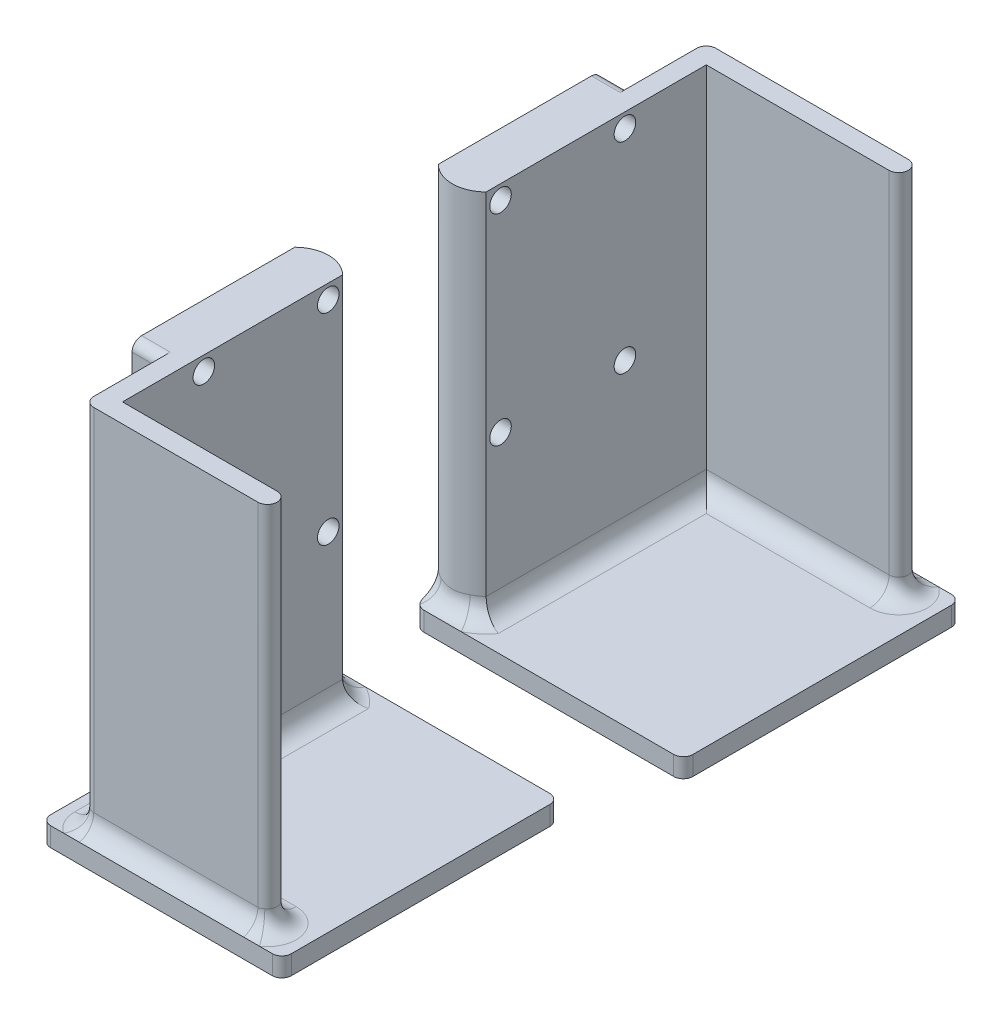
SolidWorks part; units mm, degrees
ref_plane "Front Plane" through (0, 0, 0) normal (0, 0, 1) x (1, 0, 0)
ref_plane "Top Plane" through (0, 0, 0) normal (0, 1, 0) x (1, 0, 0)
ref_plane "Right Plane" through (0, 0, 0) normal (1, 0, 0) x (0, 0, -1)
sketch "Sketch5" plane through (0, 0, 0) normal (0, 1, 0) x (1, 0, 0)
  line L0 (-1000, 0) -> (49000, 0) construction
sketch "Sketch1" plane through (0, 0, 0) normal (0, 1, 0) x (1, 0, 0)
  line L0 (-201000, 0) -> (249000, 0) construction
  line L1 (-28.1, 34) -> (0, 34)
  line L2 (-28.1, 34) -> (-28.1, 5)
  line L3 (-28.1, 5) -> (0, 5)
  line L4 (0, 34) -> (0, 5)
  line L5 (-28.1, 34) -> (0, 5) construction
  line L6 (-28.1, 5) -> (0, 34) construction
  line L7 (-55, 0) -> (55, 0) construction
  line L8 (-28.1, -5) -> (-2.95, -34) construction
  line L9 (-28.1, -34) -> (-2.95, -5) construction
  line L10 (-2.95, -34) -> (-2.95, -5)
  line L11 (-28.1, -5) -> (-2.95, -5)
  line L12 (-28.1, -34) -> (-28.1, -5)
  line L13 (-28.1, -34) -> (-2.95, -34)
  point P0 (-14.05, 19.5)
  point P14 (-13, -19.5)
  dimension "D1" = 29
  dimension "D2" = 28.1
  dimension "D3" = 5
  dimension "D4" = 0
  dimension "D5" = 25.15
extrude "Boss-Extrude1" add sketch "Sketch1" along normal blind 2
sketch "Sketch2" plane through (0, 2, 0) normal (0, 1, 0) x (1, 0, 0)
  line L0 (-28.1, 19.5) -> (0, 19.5) construction
  line L1 (-24.1, 31.5) -> (-24.1, 7.5) construction
  line L2 (-23.1, 31.5) -> (-23.1, 7.5)
  line L3 (-25.1, 31.5) -> (-25.1, 7.5)
  line L4 (0, 5) -> (0, 34)
  line L5 (0, 34) -> (-28.1, 34)
  line L6 (-28.1, 34) -> (-28.1, 5)
  line L7 (-28.1, 5) -> (0, 5)
  line L8 (0, 5) -> (0, 34)
  line L9 (0, 34) -> (-28.1, 34)
  line L10 (-28.1, 34) -> (-28.1, 5)
  line L11 (-28.1, 5) -> (0, 5)
  line L12 (-25.1, 7.5) -> (-23.1, 7.5) construction
  line L13 (-1000, 0) -> (49000, 0) construction
  line L16 (-24.1, 31.5) -> (-4, 31.5) construction
  line L17 (-24.1, 32.5) -> (-4, 32.5)
  line L18 (-24.1, 30.5) -> (-4, 30.5)
  line L19 (-24.1, -31.5) -> (-6.95, -31.5) construction
  line L23 (-25.1, 7.5) -> (-28.1, 7.5)
  line L24 (-24.1, -32.5) -> (-6.95, -32.5)
  line L25 (-24.1, -30.5) -> (-6.95, -30.5)
  line L26 (-23.1, -31.5) -> (-23.1, -7.5)
  line L27 (-25.1, -7.5) -> (-28.1, -7.5)
  line L28 (-25.1, -31.5) -> (-25.1, -7.5)
  line L29 (-2.95, -34) -> (-2.95, -5) construction
  arc A0 (-23.1, 31.5) -> (-25.1, 31.5) centre (-24.1, 31.5) ccw
  arc A4 (-24.1, 32.5) -> (-24.1, 30.5) centre (-24.1, 31.5) ccw
  arc A5 (-4, 30.5) -> (-4, 32.5) centre (-4, 31.5) ccw
  arc A8 (-23.1, 7.5) -> (-28.1, 7.5) centre (-25.6, 10) cw
  arc A9 (-24.1, -32.5) -> (-24.1, -30.5) centre (-24.1, -31.5) cw
  arc A10 (-6.95, -30.5) -> (-6.95, -32.5) centre (-6.95, -31.5) cw
  arc A11 (-23.1, -31.5) -> (-25.1, -31.5) centre (-24.1, -31.5) cw
  arc A12 (-23.1, -7.5) -> (-28.1, -7.5) centre (-25.6, -10) ccw
  point P8 (-24.15, 19.5)
  point P16 (-24.1, 7.5)
  point P18 (-15.525, -31.5)
  point P24 (-14.05, 31.5)
  dimension "D9" = 3.5355
  dimension "D2" = 24
  dimension "D3" = 2
  dimension "D4" = 3
  dimension "D5" = 2
  dimension "D6" = 4
  dimension "D7" = 4
  dimension "D8" = 2
  dimension "D10" = 2.5
  dimension "D1" = 0
extrude "Boss-Extrude2" add sketch "Sketch2" along normal blind 38.6 contours L3 L23 A8 L2 A0 | L18 A5 L17 A4 | A12 L27 L28 A11 L26 | L24 A10 L25 A9
sketch "Sketch3" plane through (-25.1, 0, 0) normal (-1, 0, 0) x (0, 0, 1)
  line L0 (-24.5, 39.6) -> (-24.5, 2)
  line L1 (-16, -972.3653) -> (-16, 49027.6347) construction
  line L2 (0, -1.1) -> (0, 1.1) construction
  line L3 (24.5, 39.6) -> (24.5, 2)
  line L4 (-31.5, 2) -> (-7.5, 2)
  line L5 (-7.5, 2) -> (-7.5, 40.6)
  line L6 (-7.5, 40.6) -> (-31.5, 40.6)
  line L7 (-31.5, 40.6) -> (-31.5, 2)
  line L8 (-31.5, 2) -> (-7.5, 2)
  line L10 (-7.5, 40.6) -> (-31.5, 40.6)
  line L11 (-31.5, 40.6) -> (-31.5, 2)
  line L12 (7.5, 40.6) -> (23.5, 40.6)
  line L13 (24.5, 2) -> (7.5, 2)
  line L14 (7.5, 2) -> (7.5, 40.6)
  line L15 (31.5, 2) -> (7.5, 2) construction
  line L19 (-7.5, 2) -> (-7.5, 40.6)
  arc A0 (-24.5, 39.6) -> (-23.5, 40.6) centre (-23.5, 39.6) cw
  arc A3 (24.5, 39.6) -> (23.5, 40.6) centre (23.5, 39.6) ccw
  line M5 (-31.5, 2) -> (-7.5, 2)
  line M7 (-7.5, 40.6) -> (-31.5, 40.6)
  dimension "D4" = 1
  dimension "D2" = 17
  dimension "D3" = 8.5
  dimension "D1" = 0
extrude "Boss-Extrude3" add sketch "Sketch3" along normal blind 3 contours L1 L8 L10 | L1 A0 L0 M5 M7 | L14 L12 A3 L3 L13 region at (-25.1, 21.2875, -20.2474) region at (-25.1, 21.3, -11.75)
fillet "Fillet1" radius 2 6 edges at (-25.1, 2, -28) (-24.8071, 2, -32.2071) (-23.1, 2, -19) (-3, 2, -31.5) (-13.55, 2, -30.5) (-25.6, 2, -6.4645)
fillet "Fillet3" radius 2 6 edges at (-25.6, 2, 6.4645) (-15.025, 2, 30.5) (-5.95, 2, 31.5) (-24.8071, 2, 32.2071) (-23.1, 2, 19) (-25.1, 2, 28)
sketch "Sketch4" plane through (-28.1, 0, 0) normal (-1, 0, 0) x (0, 0, 1)
  line L0 (-15.5, -981.5649) -> (-15.5, 49018.4351) construction
  line L1 (-1018.5962, 28.6) -> (48981.4038, 28.6) construction
  line L3 (0, -1.1) -> (0, 1.1) construction
  line L8 (-34, 0) -> (-5, 0)
  line L9 (-5, 0) -> (-5, 2)
  line L10 (-5, 2) -> (-5.0612, 2)
  line L11 (-7.5, 4) -> (-7.5, 40.6)
  line L12 (-7.5, 40.6) -> (-23.5, 40.6)
  line L13 (-24.5, 39.6) -> (-24.5, 2)
  line L14 (-24.5, 2) -> (-34, 2)
  line L15 (-34, 2) -> (-34, 0)
  line L16 (-34, 0) -> (-5, 0)
  line L17 (-5, 0) -> (-5, 2)
  line L18 (-5, 2) -> (-5.0612, 2)
  line L20 (-7.5, 40.6) -> (-23.5, 40.6)
  line L21 (-24.5, 39.6) -> (-24.5, 2)
  line L22 (-24.5, 2) -> (-34, 2)
  line L23 (-34, 2) -> (-34, 0)
  line L27 (-7.5, 4) -> (-7.5, 40.6)
  circle A0 centre (-9, 39.1) radius 1.125
  circle A1 centre (-22, 39.1) radius 1.125
  arc A3 (-23.5, 40.6) -> (-24.5, 39.6) centre (-23.5, 39.6) ccw
  arc A5 (-23.5, 40.6) -> (-24.5, 39.6) centre (-23.5, 39.6) ccw
  circle A6 centre (-9, 18.1) radius 1.125
  circle A7 centre (-22, 18.1) radius 1.125
  circle A8 centre (22, 18.1) radius 1.125
  circle A9 centre (9, 18.1) radius 1.125
  circle A10 centre (9, 39.1) radius 1.125
  circle A11 centre (22, 39.1) radius 1.125
  spline S1 degree 3 poles (438.7043, 1951.8947) (64.8626, 169.7195) (11.5962, -3.8003) (-6.0432, 2.1879) (-6.1776, 2.2458) (-6.4321, 2.38) (-6.5535, 2.4567) (-6.7838, 2.63) (-6.8933, 2.7275) (-7.0901, 2.938) (-7.1785, 3.0517) (-7.3303, 3.2999) (-7.3917, 3.4316) (-10.0902, 12.2055) (62.281, 50.2811) (1203.6718, -1586.1077) knots -15.788524 -15.788524 -15.788524 -15.788524 0.25 0.25 0.375 0.375 0.5 0.5 0.625 0.625 0.75 0.75 0.875 0.875 8.685776 8.685776 8.685776 8.685776 only from (-5.0612, 2) to (-7.5, 4)
  spline S2 degree 3 poles (-5.0612, 2) (-5.3524, 2) (-5.634, 2.049) (-6.0432, 2.1879) (-6.1776, 2.2458) (-6.4321, 2.38) (-6.5535, 2.4567) (-6.7838, 2.63) (-6.8933, 2.7275) (-7.0901, 2.938) (-7.1785, 3.0517) (-7.3303, 3.2999) (-7.3917, 3.4316) (-7.4767, 3.708) (-7.5, 3.8537) (-7.5, 4) knots 0 0 0 0 0.25 0.25 0.375 0.375 0.5 0.5 0.625 0.625 0.75 0.75 0.875 0.875 1 1 1 1
  dimension "D3" = 2.25
  dimension "D2" = 1.5
  dimension "D4" = 8
  dimension "D5" = 1.5
  dimension "D6" = 12
  dimension "D1" = 0
extrude "Cut-Extrude1" cut sketch "Sketch4" against normal through all contours A0 | A7 | A6 | A1 | A10 | A11 | A8 | A9
fillet "Fillet2" radius 1 4 edges at (-28.1, 1, -34) (0, 1, -34) (-28.1, 1, -5) (0, 1, -5)
fillet "Fillet4" radius 1 4 edges at (-28.1, 1, 5) (-2.95, 1, 5) (-2.95, 1, 34) (-28.1, 1, 34)
